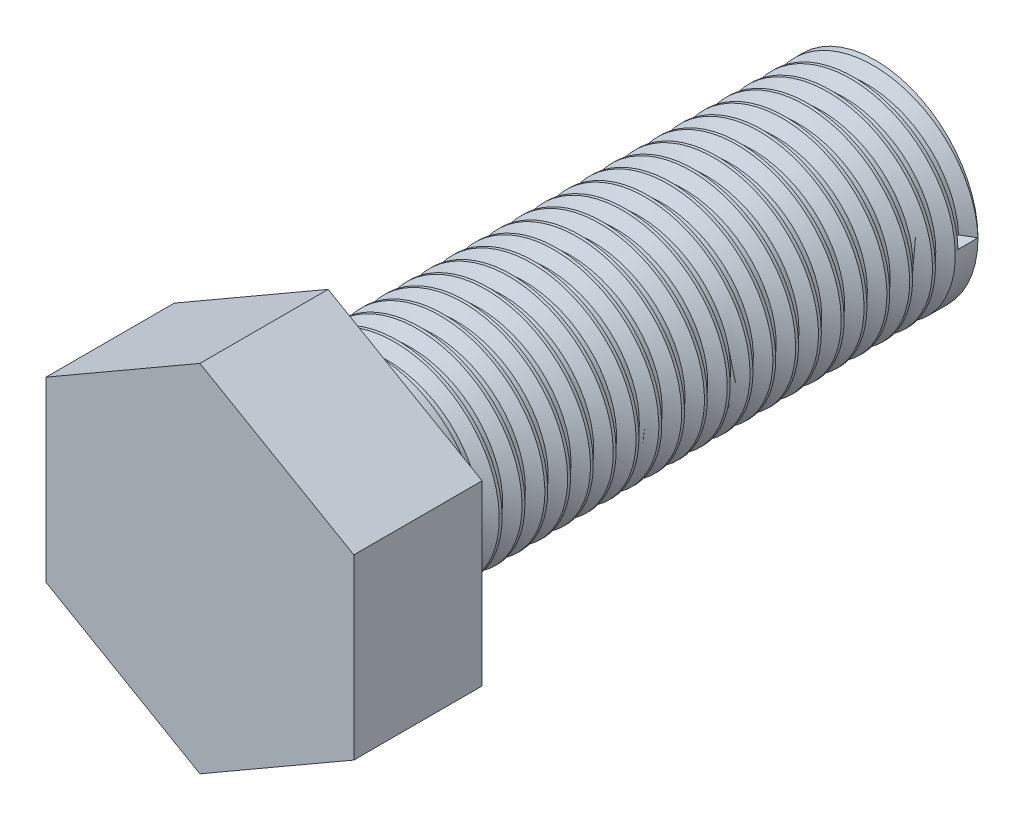
SolidWorks part; units mm, degrees
ref_plane "Front Plane" through (0, 0, 0) normal (0, 0, 1) x (1, 0, 0)
ref_plane "Top Plane" through (0, 0, 0) normal (0, 1, 0) x (1, 0, 0)
ref_plane "Right Plane" through (0, 0, 0) normal (1, 0, 0) x (0, 0, -1)
sketch "Sketch1" plane through (0, 0, 0) normal (0, 0, 1) x (1, 0, 0)
  circle A0 centre (0, 0) radius 4.7625
  dimension "D1" = 9.525
extrude "Boss-Extrude1" add sketch "Sketch1" along normal mid plane 25.4
sketch "Sketch2" plane through (0, 0, 12.7) normal (0, 0, 1) x (1, 0, 0)
  line L0 (-10.8253, 0) -> (10.8253, 0) construction
  line L1 (0, -7.5724) -> (0, 7.5724) construction
  line L3 (0, 8.2489) -> (-7.1438, 4.1244)
  line L4 (-7.1438, 4.1244) -> (-7.1438, -4.1244)
  line L5 (-7.1438, -4.1244) -> (0, -8.2489)
  line L6 (0, -8.2489) -> (7.1437, -4.1244)
  line L7 (7.1437, -4.1244) -> (7.1437, 4.1244)
  line L8 (7.1437, 4.1244) -> (0, 8.2489)
  circle A0 centre (0, 0) radius 7.1438 construction
  point P4 (0, 0)
  point P8 (0, 0)
  dimension "D1" = 14.2875
extrude "Boss-Extrude2" add sketch "Sketch2" along normal blind 5.9531
thread "Thread1" pitch 1.0583 method cut profile "Thread Profile1" start angle 0, offset 0, length 22.86, pitch 1.0583, diameter 9.525
ref_plane "Plane1" through (4.7625, 0, -12.7) normal (0, -1, 0) x (1, 0, 0)
sketch "Thread Profile1" plane through (4.7625, 0, -12.7) normal (0, -1, 0) x (1, 0, 0)
  line L0 (0, 0) -> (0, 1.0583) construction
  line L11 (0, 0) -> (0, 0.926)
  line L12 (0, 0.926) -> (-0.5728, 0.5953)
  line L13 (-0.5728, 0.5953) -> (-0.5728, 0.3307)
  line L15 (-0.5728, 0.3307) -> (0, 0)
  line L17 (-0.5728, 0.463) -> (0, 0.463) construction
  point P2 (0, 0)
  dimension "Pitch" = 1.0583
  dimension "Profile_Angle" = 60
  dimension "Profile_Land" = 0.2646
  dimension "Profile_Height" = 0.5728
